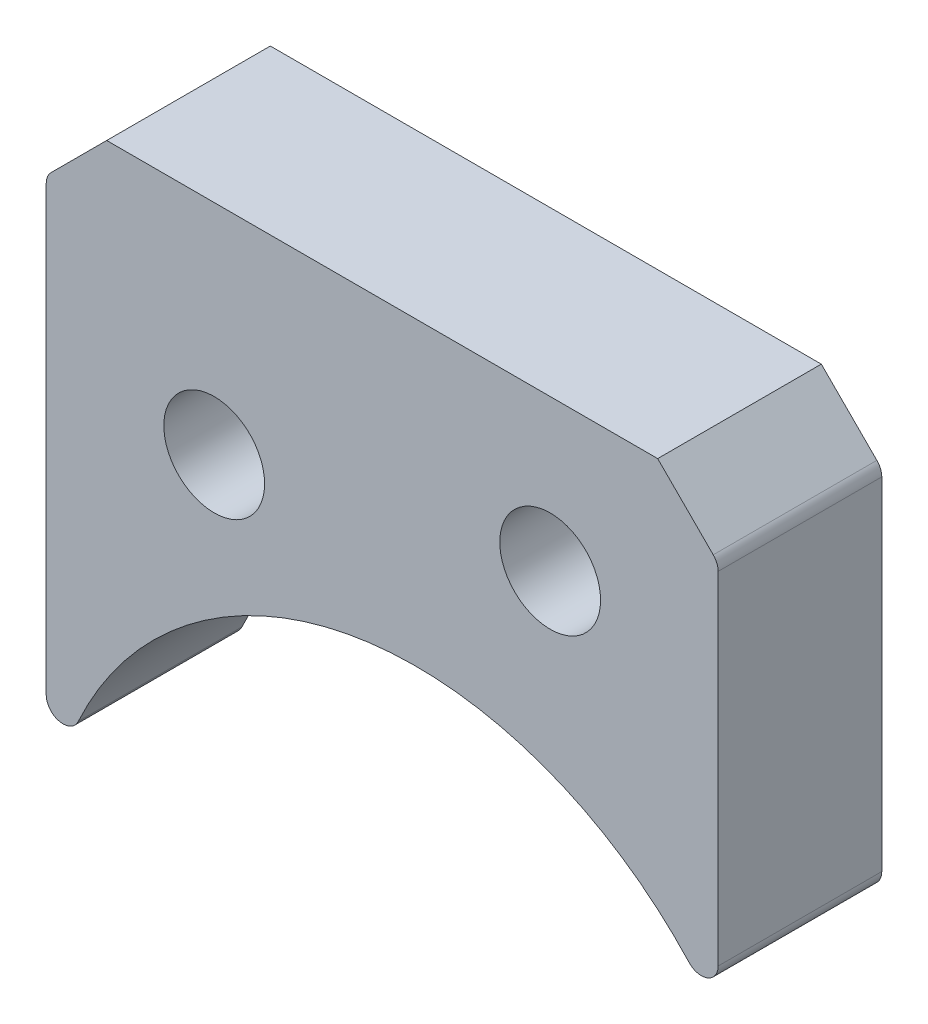
SolidWorks part; units mm, degrees
ref_plane "Front Plane" through (0, 0, 0) normal (0, 0, 1) x (1, 0, 0)
ref_plane "Top Plane" through (0, 0, 0) normal (0, 1, 0) x (1, 0, 0)
ref_plane "Right Plane" through (0, 0, 0) normal (1, 0, 0) x (0, 0, -1)
sketch "Sketch1" plane through (0, 0, 0) normal (0, 0, 1) x (1, 0, 0)
  line L2 (0, 1.05) -> (0, 20)
  line L3 (0, 20) -> (20, 20)
  line L4 (20, 6.4111) -> (20, 20)
  arc A1 (20, 6.4111) -> (0, 1.05) centre (11, 0) ccw
extrude "Boss-Extrude1" add sketch "Sketch1" along normal blind 4.87
sketch "Sketch2" plane through (0, 0, 4.87) normal (0, 0, 1) x (1, 0, 0)
  line L0 (5, 15.5) -> (11, 15.5) construction
  line L1 (11, 15.5) -> (15, 15.5) construction
  line L2 (11, 15.5) -> (11, 0) construction
  line L3 (5, 15.5) -> (5, 13.5) construction
  circle A0 centre (5, 13.5) radius 1.5
  circle A1 centre (15, 15.5) radius 1.5
extrude "Cut-Extrude1" cut sketch "Sketch2" against normal blind 4.87
chamfer "Chamfer1" distance 1.8 angle 45 2 edges at (0, 20, 2.435) (20, 20, 2.435)
fillet "Fillet1" radius 0.5 4 edges at (20, 18.2, 2.435) (0, 18.2, 2.435) (0, 1.05, 2.435) (20, 6.4111, 2.435)
